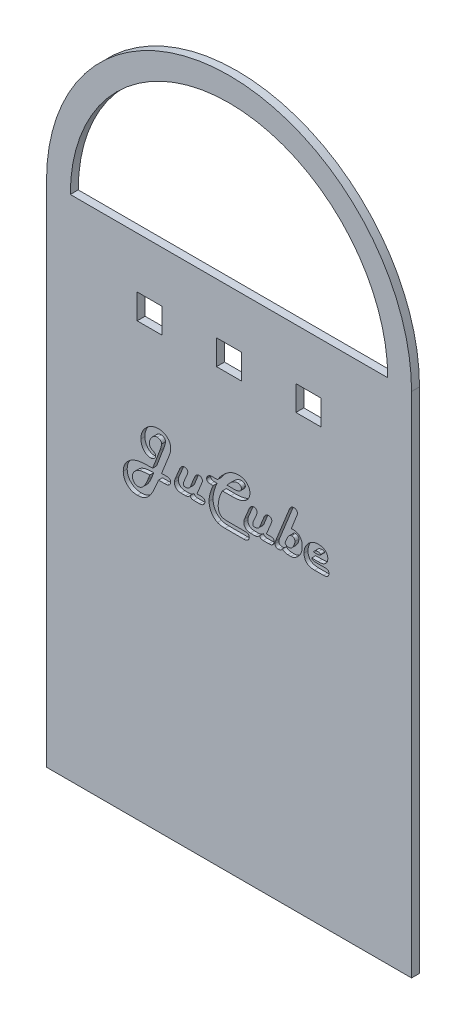
SolidWorks part; units mm, degrees
ref_plane "Front" through (0, 0, 0) normal (0, 0, 1) x (1, 0, 0)
ref_plane "Top" through (0, 0, 0) normal (0, 1, 0) x (1, 0, 0)
ref_plane "Right" through (0, 0, 0) normal (1, 0, 0) x (0, 0, -1)
sketch "Sketch2" plane through (0, 0, 0) normal (0, 0, 1) x (1, 0, 0)
  line L0 (0, 0) -> (146.05, 0)
  line L1 (146.05, 0) -> (146.05, 203.2)
  line L2 (0, 203.2) -> (0, 0)
  line L3 (9.525, 203.2) -> (136.525, 203.2)
  line L4 (41.275, 203.2) -> (41.275, -49796.8) construction
  line L5 (73.025, 203.2) -> (73.025, -49796.8) construction
  line L6 (104.775, 203.2) -> (104.775, -49796.8) construction
  line L7 (40.1195, 177.8) -> (50040.1195, 177.8) construction
  line L9 (36.275, 182.8) -> (46.275, 182.8)
  line L10 (36.275, 182.8) -> (36.275, 172.8)
  line L11 (36.275, 172.8) -> (46.275, 172.8)
  line L12 (46.275, 182.8) -> (46.275, 172.8)
  line L13 (36.275, 182.8) -> (46.275, 172.8) construction
  line L14 (36.275, 172.8) -> (46.275, 182.8) construction
  line L15 (68.025, 182.8) -> (78.025, 182.8)
  line L16 (68.025, 182.8) -> (68.025, 172.8)
  line L17 (68.025, 172.8) -> (78.025, 172.8)
  line L18 (78.025, 182.8) -> (78.025, 172.8)
  line L19 (68.025, 182.8) -> (78.025, 172.8) construction
  line L20 (68.025, 172.8) -> (78.025, 182.8) construction
  line L21 (99.775, 182.8) -> (109.775, 182.8)
  line L22 (99.775, 182.8) -> (99.775, 172.8)
  line L23 (99.775, 172.8) -> (109.775, 172.8)
  line L24 (109.775, 182.8) -> (109.775, 172.8)
  line L25 (99.775, 182.8) -> (109.775, 172.8) construction
  line L26 (99.775, 172.8) -> (109.775, 182.8) construction
  arc A0 (0, 203.2) -> (146.05, 203.2) centre (73.025, 203.2) cw
  arc A1 (9.525, 203.2) -> (136.525, 203.2) centre (73.025, 203.2) cw
  point P9 (73.025, 203.2)
  point P18 (41.275, 177.8)
  point P23 (73.025, 177.8)
  point P28 (104.775, 177.8)
  point P36 (142.7041, 214.0138)
  dimension "D1" = 203.2
  dimension "D2" = 146.05
  dimension "D3" = 127
  dimension "D4" = 25.4
  dimension "D5" = 31.75
  dimension "D6" = 31.75
  dimension "D7" = 10
  dimension "D8" = 10
extrude "Boss-Extrude5" add sketch "Sketch2" along normal blind 3.175
sketch "Sketch4" plane through (0, 0, 3.175) normal (0, 0, 1) x (1, 0, 0)
  line L0 (36.275, 254) -> (36.275, -49746) construction
  line L1 (36.275, 182.8) -> (36.275, 172.8) construction
  line L2 (109.775, 254) -> (109.775, -49746) construction
  line L3 (109.775, 172.8) -> (109.775, 182.8) construction
  text T0 "JuCube" font "Harlow Solid Italic" height 17.78
  point P5 (36.275, 177.8)
  point P10 (109.775, 177.8)
  point P11 (36.275, 121.2416)
  point P12 (36.275, 119.7055)
  point P13 (0, 0)
  point P14 (30.4624, 121.8999)
  point P15 (0, 0)
  point P16 (0, 0)
  point P17 (0, 0)
extrude "Cut-Extrude2" cut sketch "Sketch4" against normal blind 1.5875
